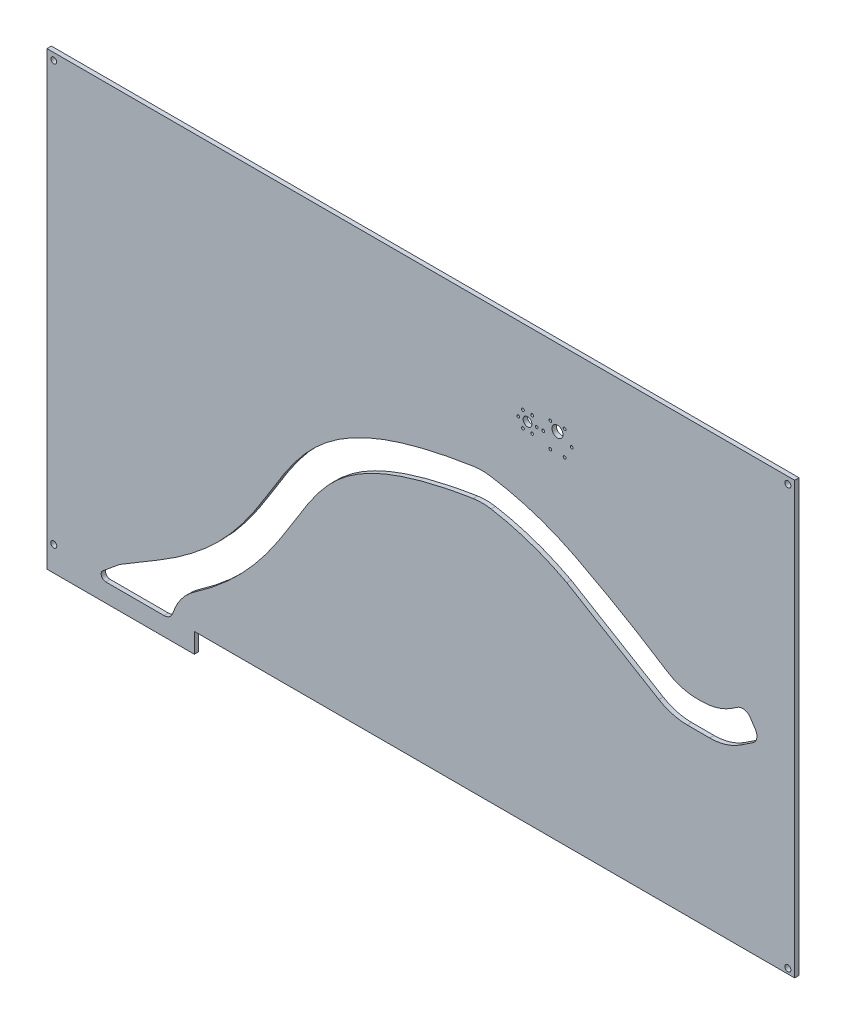
SolidWorks part; units mm, degrees
ref_plane "前视基准面" through (0, 0, 0) normal (0, 0, 1) x (1, 0, 0)
ref_plane "上视基准面" through (0, 0, 0) normal (0, 1, 0) x (1, 0, 0)
ref_plane "右视基准面" through (0, 0, 0) normal (1, 0, 0) x (0, 0, -1)
sketch "Sketch1" plane through (0, 0, 0) normal (0, 0, 1) x (1, 0, 0)
  line L0 (86.3892, 46.5642) -> (136.3892, 46.5642) construction
  line L1 (136.3892, 46.5642) -> (169.6686, 68.4983) construction
  line L2 (-475, -100) -> (-518.0311, -125.7444)
  line L3 (-459.5978, -125.7444) -> (-459.5978, -149.5504)
  line L4 (81.7745, 31.5642) -> (140.8878, 31.5642)
  line L5 (-467.2989, -112.8722) -> (-510.33, -138.6166) construction
  line L6 (140.8878, 31.5642) -> (177.9233, 55.9739)
  line L7 (-459.5978, -149.5504) -> (-546.7804, -149.5504)
  line L8 (-436.8168, -147.9944) -> (215.0808, -147.9944)
  line L9 (215.0808, -147.9944) -> (215.0808, 320)
  line L10 (215.0808, 320) -> (-596.8168, 320)
  line L11 (-596.8168, -150) -> (-596.8168, 320)
  line L12 (215.0808, -147.9944) -> (-596.8168, 320) construction
  line L13 (215.0808, 320) -> (-596.8168, -150) construction
  line L14 (-518.0311, -125.7444) -> (-459.5978, -125.7444) construction
  line L15 (-518.0311, -125.7444) -> (-546.7804, -149.5504)
  line L16 (-436.8168, -147.9944) -> (-436.8168, -169.5504)
  line L17 (90.9712, 61.5642) -> (131.8907, 61.5642)
  line L18 (-596.8168, -150) -> (-596.8168, -169.5504)
  line L19 (-596.8168, -169.5504) -> (-436.8168, -169.5504)
  line L21 (-32.3237, 100) -> (135.1953, 100) construction
  line L22 (-25, 130) -> (125, 130) construction
  line L23 (-28.6108, 115) -> (130.0228, 115) construction
  line L24 (131.8907, 61.5642) -> (161.4139, 81.0227)
  line L25 (177.9233, 55.9739) -> (161.4139, 81.0227)
  line L26 (-21.7014, 128.3139) -> (-25, 130)
  line L27 (-32.3237, 100) -> (81.7745, 31.5642)
  arc A0 (-125, 160) -> (-25, 130) centre (-159.8893, -137.9643) cw
  arc A1 (-28.6108, 115) -> (86.3892, 46.5642) centre (-559.3589, -907.7137) cw construction
  arc A2 (-124.7147, 129.7347) -> (-32.3237, 100) centre (-159.8893, -137.9643) cw
  circle A3 centre (-75, 230) radius 10 construction
  arc A4 (-124.84, 144.8723) -> (-28.6108, 115) centre (-159.8893, -137.9643) cw construction
  arc A5 (-21.7014, 128.3139) -> (90.9712, 61.5642) centre (-559.3589, -907.7137) cw
  circle A6 centre (-589.3757, -142.5578) radius 3.2924
  circle A7 centre (207.6422, -142.5578) radius 3.2924
  circle A8 centre (207.6422, 312.5578) radius 3.2944
  circle A9 centre (-589.3757, 312.5578) radius 3.1635
  arc A10 (135.1953, 100) -> (187.8618, 132.897) centre (303.6181, -111.0302) cw construction
  arc A11 (130.0228, 115) -> (181.4309, 146.4485) centre (303.6181, -111.0302) cw construction
  arc A12 (125, 130) -> (175, 160) centre (303.6181, -111.0302) cw construction
  arc A13 (-35.5202, 101.6861) -> (81.7745, 31.5642) centre (-559.3589, -907.7137) cw construction
  circle A14 centre (-85, 230) radius 1.5
  circle A15 centre (-80, 238.6603) radius 1.5
  circle A16 centre (-70, 238.6603) radius 1.5
  circle A17 centre (-65, 230) radius 1.5
  circle A18 centre (-70, 221.3397) radius 1.5
  circle A19 centre (-80, 221.3397) radius 1.5
  circle A20 centre (-42.5, 230) radius 15.5 construction
  circle A21 centre (-58, 230) radius 1.5
  circle A22 centre (-50.25, 243.4234) radius 1.5
  circle A23 centre (-34.75, 243.4234) radius 1.5
  circle A24 centre (-27, 230) radius 1.5
  circle A25 centre (-34.75, 216.5766) radius 1.5
  circle A26 centre (-50.25, 216.5766) radius 1.5
  circle A27 centre (-75, 230) radius 4.7625
  circle A28 centre (-42.5, 237) radius 6
  spline S0 degree 3 poles (-475, -100) (-419.5406, -66.8201) (-329.5908, 43.116) (-307.6356, 134.2871) (-125, 160) knots 0 0 0 0 0.312224 1 1 1 1
  spline S1 degree 1 poles (-459.5978, -125.7444) (-124.7147, 129.7347) knots 0 0 1 1 construction
  spline S2 degree 3 poles (-459.5978, -125.7444) (-458.1292, -124.8657) (-455.1858, -123.0815) (-449.4714, -119.5247) (-442.5555, -115.0462) (-434.6362, -109.6397) (-424.5564, -102.3861) (-412.8294, -93.2453) (-400.0558, -82.1905) (-388.4865, -71.0922) (-374.5374, -56.3046) (-359.6201, -37.9792) (-344.8908, -16.7676) (-332.3401, 3.2457) (-321.0552, 21.7964) (-310.226, 38.6648) (-299.0796, 53.8348) (-286.8128, 67.5146) (-272.4318, 80.0885) (-257.6527, 89.9241) (-243.4982, 97.442) (-231.5651, 102.8866) (-218.1727, 108.1127) (-203.191, 113.0878) (-189.2817, 116.9961) (-177.2434, 119.9629) (-167.7458, 122.1041) (-157.766, 124.1573) (-149.0369, 125.7919) (-141.7993, 127.0518) (-136.2431, 127.9723) (-131.5022, 128.7191) (-127.6487, 129.3032) (-125.6903, 129.5925) (-124.7147, 129.7347) knots 0 0 0 0 0.007773 0.015545 0.03109 0.046636 0.062181 0.093271 0.124361 0.155452 0.186542 0.248723 0.310904 0.373084 0.435265 0.497446 0.559626 0.621807 0.683988 0.746169 0.777259 0.808349 0.83944 0.87053 0.90162 0.917166 0.932711 0.948256 0.963801 0.971574 0.979346 0.987119 0.991005 0.994892 0.994892 0.994892 0.994892
  spline S3 degree 1 poles (-467.2989, -112.8722) (-124.84, 144.8723) knots 0 0 1 1 construction
  spline S4 degree 3 poles (-467.2989, -112.8722) (-465.8766, -112.0213) (-463.025, -110.2926) (-457.4973, -106.8516) (-450.8174, -102.5249) (-443.1848, -97.3122) (-433.4896, -90.3317) (-422.2436, -81.559) (-410.0336, -70.981) (-398.9994, -60.3828) (-385.707, -46.2708) (-371.4731, -28.7597) (-357.2741, -8.2881) (-344.9599, 11.3612) (-333.6257, 29.9919) (-322.417, 47.4318) (-310.4985, 63.6121) (-297.0179, 78.5777) (-281.0248, 92.4603) (-264.7088, 103.2127) (-249.3105, 111.3089) (-236.4572, 117.1105) (-222.1723, 122.621) (-206.3349, 127.8161) (-191.7467, 131.8615) (-179.1859, 134.915) (-169.3063, 137.1107) (-158.9544, 139.2089) (-149.9221, 140.8739) (-142.4479, 142.1541) (-136.7117, 143.0887) (-130.8627, 143.9946) (-126.8382, 144.5862) (-124.84, 144.8723) knots 0 0 0 0 0.007793 0.015586 0.031173 0.046759 0.062345 0.093518 0.12469 0.155863 0.187036 0.249381 0.311726 0.374071 0.436417 0.498762 0.561107 0.623452 0.685798 0.748143 0.779315 0.810488 0.841661 0.872833 0.904006 0.919592 0.935179 0.950765 0.966351 0.974144 0.981937 0.989731 0.997524 0.997524 0.997524 0.997524 construction
  point P38 (-190, 85.5025)
  point P62 (-75, 230)
  dimension "D5" = 300
  dimension "D8" = 15
  dimension "D14" = 470
  dimension "D18" = 70
  dimension "D19" = 31
  dimension "D20" = 3
  dimension "D21" = 6
  dimension "D22" = 651.8975
  dimension "D23" = 32.5
  dimension "D24" = 50
  dimension "D26" = 6
  dimension "D27" = 3
  dimension "D29" = 20
  dimension "D30" = 9.525
  dimension "D1" = 105
  dimension "D2" = 100
  dimension "D3" = 350
  dimension "D4" = 260
  dimension "D6" = 100
  dimension "D7" = 30
  dimension "D9" = 15
  dimension "D10" = 115
  dimension "D11" = 50
  dimension "D13" = 15
  dimension "D15" = 190
  dimension "D16" = 320
  dimension "D17" = 20
  dimension "D25" = 811.9
  dimension "D28" = 70
  dimension "D12" = 30
extrude "Boss-Extrude1" add sketch "Sketch1" along normal blind 4.7625
fillet "Fillet2" radius 10 3 edges at (161.4139, 81.0227, 2.3813) (177.9233, 55.9739, 2.3813) (-459.5978, -149.5504, 2.3813)
fillet "Fillet1" radius 60 7 edges at (81.7745, 31.5642, 2.3813) (140.8878, 31.5642, 2.3813) (-459.5978, -125.7444, 2.3813) (-124.7147, 129.7347, 2.3813) (-125, 160, 2.3813) (90.9712, 61.5642, 2.3813) (131.8907, 61.5642, 2.3813)
fillet "Fillet3" radius 5 1 edges at (-546.7804, -149.5504, 2.3813)
